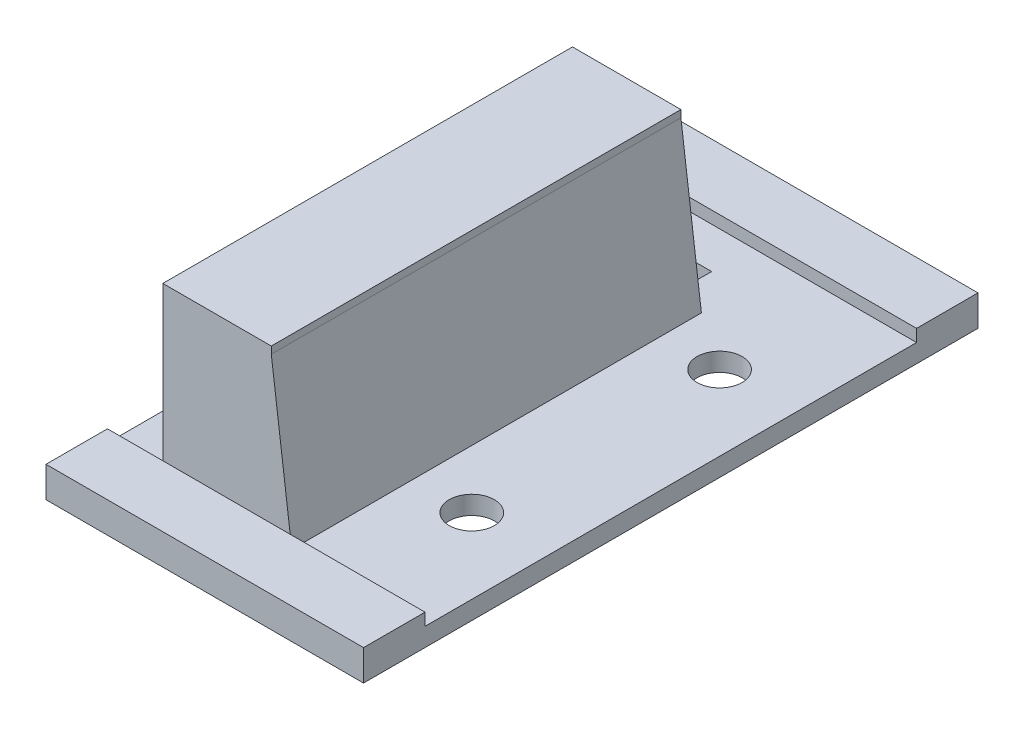
SolidWorks part; units mm, degrees
ref_plane "Front Plane" through (0, 0, 0) normal (0, 0, 1) x (1, 0, 0)
ref_plane "Top Plane" through (0, 0, 0) normal (0, 1, 0) x (1, 0, 0)
ref_plane "Right Plane" through (0, 0, 0) normal (1, 0, 0) x (0, 0, -1)
sketch "Sketch2" plane through (0, 0, 0) normal (0, 1, 0) x (1, 0, 0)
  line L0 (0, 38.1) -> (39.3827, 38.1) construction
  line L1 (0, 0) -> (39.3827, 0)
  line L2 (0, 0) -> (0, 76.2)
  line L3 (0, 76.2) -> (39.3827, 76.2)
  line L4 (39.3827, 0) -> (39.3827, 76.2)
  line L5 (30.0679, 38.1) -> (30.0679, 53.467) construction
  line L6 (30.0679, 38.1) -> (30.0679, 22.733) construction
  line L7 (39.3827, 68.58) -> (0, 68.58)
  line L8 (19.05, 38.1) -> (19.05, 63.5)
  line L9 (19.05, 63.5) -> (11.176, 63.5)
  line L10 (11.176, 63.5) -> (11.176, 12.7)
  line L11 (11.176, 12.7) -> (19.05, 12.7)
  line L12 (19.05, 12.7) -> (19.05, 38.1)
  line L13 (33.1404, 76.2) -> (33.1404, 68.58) construction
  line L14 (28.6413, 0) -> (28.6413, 7.62) construction
  line L15 (39.3827, 7.62) -> (0, 7.62)
  line L16 (20.32, 7.62) -> (20.32, 68.58) construction
  line L17 (7.62, 68.58) -> (7.62, 7.62) construction
  line L18 (6.87, 58.42) -> (7.62, 58.42)
  line L19 (7.62, 68.58) -> (6.87, 68.58)
  line L20 (7.62, 68.58) -> (7.62, 7.62)
  line L21 (7.62, 7.62) -> (6.87, 7.62)
  line L22 (6.87, 68.58) -> (6.87, 7.62)
  line L23 (7.62, 17.78) -> (6.87, 17.78)
  circle A0 centre (30.0679, 53.467) radius 2.794
  circle A1 centre (30.0679, 22.733) radius 2.794
  dimension "D1" = 1.27
  dimension "D2" = 7.62
  dimension "D3" = 0.75
  dimension "D4" = 10.16
  dimension "D5" = 10.16
extrude "Boss-Extrude2" add sketch "Sketch2" along normal blind 3.81 contours L4 L15 L2 L1 | L7 L4 L3 L2 region at (19.6913, 0, -3.81) region at (19.6913, 0, -72.39)
extrude "Boss-Extrude3" add sketch "Sketch2<3>" along normal blind 2.286 contours L15 L4 L7 L2 A1 A0 L12 L11 L10 L9 L8 | L22 L7 L2 L15 | L22 L21 L20 L19 region at (3.435, 0, -38.1) region at (25.5409, 0, -38.1)
sketch "Sketch2<3>" plane through (0, 0, 0) normal (0, 1, 0) x (1, 0, 0) same geometry as "Sketch2"
extrude "Boss-Extrude4" add sketch "Sketch2<4>" along normal blind 22.86 contours L18 L22 L15 L20 | L20 L23 L22 L15 region at (7.245, 0, -12.7) region at (7.245, 0, -38.1)
sketch "Sketch2<4>" plane through (0, 0, 0) normal (0, 1, 0) x (1, 0, 0) same geometry as "Sketch2"
sketch "Sketch7" plane through (7.62, 0, 0) normal (1, 0, 0) x (0, 0, -1)
  line L0 (7.62, 22.86) -> (58.42, 22.86)
  line L1 (58.42, 22.86) -> (58.42, 21.971)
  line L2 (58.42, 22.86) -> (58.42, 2.286) construction
  line L3 (58.42, 21.971) -> (7.62, 21.971)
  line L4 (7.62, 22.86) -> (7.62, 3.81) construction
  line L10 (7.62, 3.81) -> (7.62, 2.286)
  line L11 (7.62, 2.286) -> (58.42, 2.286)
  line L12 (58.42, 2.286) -> (58.42, 22.86)
  line L13 (58.42, 22.86) -> (7.62, 22.86)
  line L14 (7.62, 22.86) -> (7.62, 3.81)
  line L19 (7.62, 22.86) -> (7.62, 21.971)
  dimension "D1" = 0
extrude "Boss-Extrude6" add sketch "Sketch7" along normal blind 12.7
sketch "Sketch8" plane through (0, 0, -7.62) normal (0, 0, -1) x (-1, 0, 0)
  line L0 (-7.62, 2.286) -> (-7.62, 21.971)
  line L1 (-7.62, 21.971) -> (-20.32, 21.971)
  line L2 (-20.32, 21.971) -> (-7.62, 21.971) construction
  line L3 (-20.32, 21.971) -> (-22.86, 2.286)
  line L4 (-39.3827, 2.286) -> (-7.62, 2.286) construction
  line L5 (-22.86, 2.286) -> (-7.62, 2.286)
  line L6 (-19.5517, 21.971) -> (-22.0917, 2.286)
  line L7 (-7.62, 3.81) -> (-9.144, 2.286)
  line L8 (-21.895, 3.81) -> (-21.0173, 2.286)
  line L9 (-8.9467, 21.971) -> (-7.62, 20.6443)
  line L10 (-19.689, 20.9068) -> (-17.9616, 21.971)
  line M1 (-39.3827, 2.286) -> (-7.62, 2.286)
  line M2 (-7.62, 2.286) -> (-7.62, 3.81)
  line M3 (-7.62, 3.81) -> (-39.3827, 3.81)
  dimension "D1" = 15.24
  dimension "D2" = 12.7
  dimension "D3" = 0.762
extrude "Boss-Extrude7" add sketch "Sketch8" along normal blind 0.889 contours L10 L6 L0 L9 L1 M3 | L8 L6 L5 | L7 M2 M1 | L1 L9 L0 | L6 L10 L1 | L8 L7 M3 M1 region at (8.128, 2.794, -7.62) region at (14.1945, 12.5544, -7.62) region at (14.9141, 3.0713, -7.62) region at (8.0622, 21.5288, -7.62) region at (21.668, 2.794, -7.62) region at (19.0674, 21.6163, -7.62)
extrude "Boss-Extrude8" add sketch "Sketch8<4>" along normal up to surface (50.8 mm away) contours L6 L1 L3 M3 | L6 L3 M3 M1 | L8 L6 L5 | L7 M2 M1 | L6 L10 L1 | L1 L9 L0 region at (8.128, 2.794, -7.62) region at (8.0622, 21.5288, -7.62) region at (21.1075, 12.8905, -7.62) region at (21.668, 2.794, -7.62) region at (22.3775, 3.048, -7.62) region at (19.0674, 21.6163, -7.62) up to face at (11.6033, 15.7057, -58.42)
sketch "Sketch8<4>" plane through (0, 0, -7.62) normal (0, 0, -1) x (-1, 0, 0) same geometry as "Sketch8"
sketch "Sketch10" plane through (0, 2.286, 0) normal (0, 1, 0) x (1, 0, 0)
  line L0 (21.0173, 8.509) -> (9.144, 8.509)
  line L1 (9.144, 8.509) -> (9.144, 58.42)
  line L3 (9.144, 58.42) -> (21.0173, 58.42)
  line L4 (21.0173, 58.42) -> (21.0173, 8.509)
extrude "Cut-Extrude5" cut sketch "Sketch10" against normal through all
